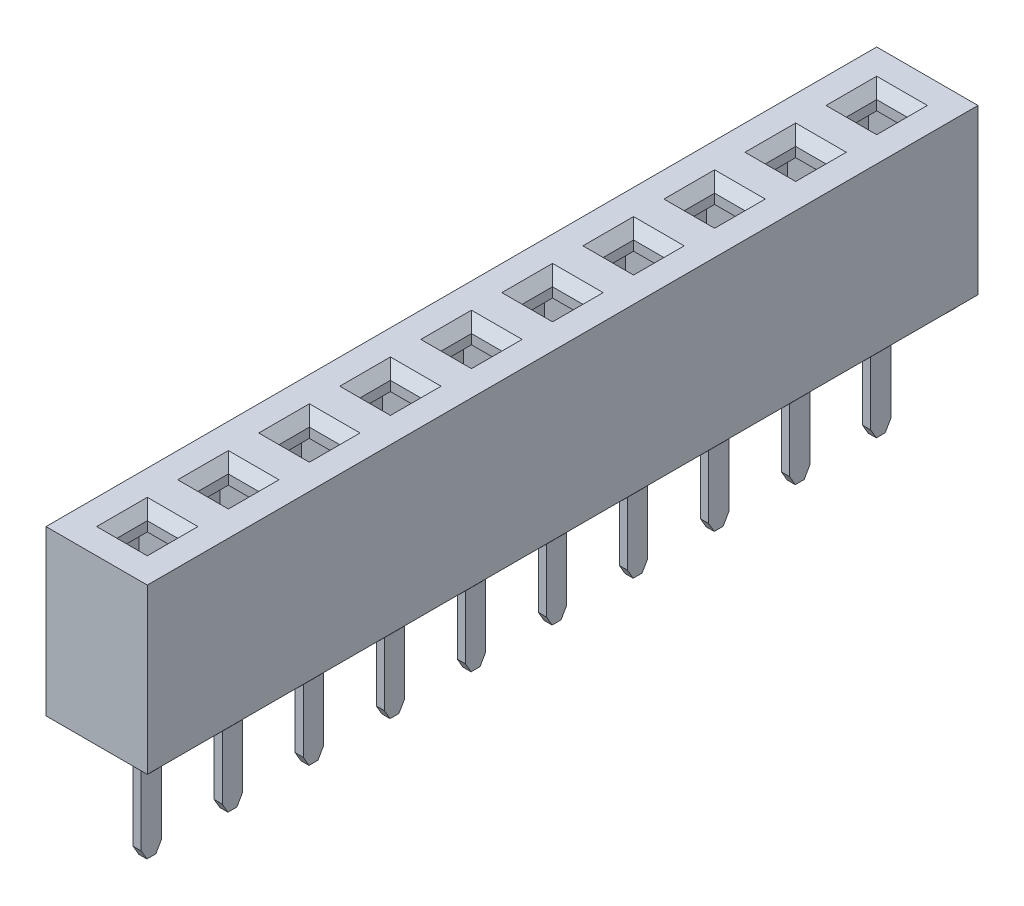
SolidWorks part; units mm, degrees
ref_plane "Front Plane" through (0, 0, 0) normal (0, 0, 1) x (1, 0, 0)
ref_plane "Top Plane" through (0, 0, 0) normal (0, 1, 0) x (1, 0, 0)
ref_plane "Right Plane" through (0, 0, 0) normal (1, 0, 0) x (0, 0, -1)
sketch "Sketch1" plane through (0, 0, 0) normal (1, 0, 0) x (0, 0, -1)
  line L0 (-1, -2.15) -> (1, -2.15)
  line L1 (-10.25, -2.15) -> (10.25, -2.15)
  line L2 (-10.25, -2.15) -> (-10.25, 2.15)
  line L3 (-10.25, 2.15) -> (10.25, 2.15)
  line L4 (10.25, -2.15) -> (10.25, 2.15)
  line L5 (-10.25, -2.15) -> (10.25, 2.15) construction
  line L6 (-10.25, 2.15) -> (10.25, -2.15) construction
  line L7 (-1, -2.15) -> (-1, -4.85) construction
  line L8 (-1.25, -4.85) -> (-0.75, -4.85)
  point P0 (0, 0)
  point P9 (0, -2.15)
  point P13 (-1, -4.85)
  dimension "D1" = 0.5
  dimension "Body Width" = 20.5
  dimension "Body Length" = 4.3
  dimension "For Hole Center to Center" = 2
  dimension "Termination Contact Length" = 2.7
  dimension "Overall Length" = 7
sketch "Sketch3" plane through (0, 0, 0) normal (0, 1, 0) x (1, 0, 0)
  line L1 (1.25, -10.25) -> (-1.25, -10.25)
  line L2 (1.25, -10.25) -> (1.25, 10.25)
  line L3 (1.25, 10.25) -> (-1.25, 10.25)
  line L4 (-1.25, -10.25) -> (-1.25, 10.25)
  line L5 (1.25, -10.25) -> (-1.25, 10.25) construction
  line L6 (1.25, 10.25) -> (-1.25, -10.25) construction
  point P0 (0, 0)
  dimension "D1" = 2.5
sketch "Sketch2" plane through (0, 0, 0) normal (1, 0, 0) x (0, 0, -1)
  line L0 (-10.25, 2.15) -> (10.25, 2.15)
  line L1 (10.25, 2.15) -> (10.25, -2.15)
  line L2 (10.25, -2.15) -> (-10.25, -2.15)
  line L3 (-10.25, -2.15) -> (-10.25, 2.15)
extrude "Boss-Extrude1" add sketch "Sketch2" against normal up to vertex (1.25 mm away) and the other way up to vertex (1.25 mm away) up to point (-1.25, 0, -10.25) other way up to point (1.25, 0, -10.25)
sketch "Sketch4" plane through (0, 2.15, 0) normal (0, 1, 0) x (1, 0, 0)
  line L0 (0, -10.25) -> (0, 10.25) construction
  line L1 (0.625, -9.625) -> (-0.625, -9.625)
  line L2 (0.625, -9.625) -> (0.625, -8.375)
  line L3 (0.625, -8.375) -> (-0.625, -8.375)
  line L4 (-0.625, -9.625) -> (-0.625, -8.375)
  line L5 (0.625, -9.625) -> (-0.625, -8.375) construction
  line L6 (0.625, -8.375) -> (-0.625, -9.625) construction
  point P0 (0, -9)
  dimension "D1" = 9
  dimension "D2" = 1.25
extrude "Cut-Extrude1" cut sketch "Sketch4" against normal through all draft 45
sketch "Sketch5" plane through (0, 2.15, 0) normal (0, 1, 0) x (1, 0, 0)
  line L1 (0.375, -9.375) -> (-0.375, -9.375)
  line L2 (0.375, -9.375) -> (0.375, -8.625)
  line L3 (0.375, -8.625) -> (-0.375, -8.625)
  line L4 (-0.375, -9.375) -> (-0.375, -8.625)
  line L5 (0.375, -9.375) -> (-0.375, -8.625) construction
  line L6 (0.375, -8.625) -> (-0.375, -9.375) construction
  point P0 (0, -9)
  dimension "D1" = 0.75
extrude "Cut-Extrude2" cut sketch "Sketch5" against normal through all
sketch "Sketch6" plane through (0, -2.15, 0) normal (0, -1, 0) x (1, 0, 0)
  line L0 (0, 10.25) -> (0, -10.25) construction
  line L1 (-0.7, 9.7) -> (0.7, 9.7)
  line L2 (-0.7, 9.7) -> (-0.7, 8.3)
  line L3 (-0.7, 8.3) -> (0.7, 8.3)
  line L4 (0.7, 9.7) -> (0.7, 8.3)
  line L5 (-0.7, 9.7) -> (0.7, 8.3) construction
  line L6 (-0.7, 8.3) -> (0.7, 9.7) construction
  line L7 (0.375, 9.375) -> (0.375, 8.625) construction
  line L8 (0.375, 8.625) -> (-0.375, 8.625) construction
  point P0 (0, 9)
  point P9 (0.375, 9)
  point P12 (0, 8.625)
  dimension "D1" = 1.4
extrude "Cut-Extrude3" cut sketch "Sketch6" against normal blind 3.81
sketch "Sketch7" plane through (0, -2.15, 0) normal (0, -1, 0) x (1, 0, 0)
  line L0 (-1.25, 9.7) -> (1.25, 9.7)
  line L1 (-1.25, 10.25) -> (-1.25, -10.25) construction
  line L2 (1.25, 10.25) -> (1.25, -10.25) construction
  line L3 (-1.25, 8.3) -> (1.25, 8.3)
  line L5 (-0.7, 8.3) -> (0.7, 8.3) construction
  line L6 (0.7, 9.7) -> (-0.7, 9.7) construction
  line L7 (1.25, 9.7) -> (1.25, 8.3)
  line L8 (-1.25, 8.3) -> (-1.25, 9.7)
extrude "Cut-Extrude4" cut sketch "Sketch7" against normal blind 0.254
pattern_linear "LPattern1" count 10 spacing 2 along (0, 0, -1) of "Cut-Extrude1", "Cut-Extrude2", "Cut-Extrude3", "Cut-Extrude4"
sketch "Sketch8" plane through (0, -2.15, 0) normal (0, -1, 0) x (1, 0, 0)
  line L0 (1.25, 9.975) -> (-1.25, 9.975)
  line L1 (1.25, 10.25) -> (1.25, 9.7) construction
  line L2 (-1.25, 10.25) -> (-1.25, 9.7) construction
  line L3 (-1.25, 9.975) -> (-1.25, 10.25)
  line L4 (-1.25, 10.25) -> (1.25, 10.25)
  line L5 (1.25, 10.25) -> (1.25, 9.975)
  line L6 (1.25, -9.975) -> (1.25, -10.25)
  line L7 (1.25, -9.7) -> (1.25, -10.25) construction
  line L8 (1.25, -10.25) -> (-1.25, -10.25)
  line L9 (-1.25, -10.25) -> (-1.25, -9.975)
  line L10 (-1.25, -9.7) -> (-1.25, -10.25) construction
  line L11 (-1.25, -9.975) -> (1.25, -9.975)
extrude "Cut-Extrude5" cut sketch "Sketch8" against normal up to surface (0.254 mm away) up to face at (-0.975, -1.896, -9)
sketch "Sketch9" plane through (0, 1.66, 0) normal (0, -1, 0) x (1, 0, 0)
  line L0 (-0.7, 9.7) -> (0.7, 9.7)
  line L1 (0.7, 9.7) -> (0.7, 8.3)
  line L2 (0.7, 8.3) -> (-0.7, 8.3)
extrude "Extrude-Thin1" add sketch "Sketch9" along normal offset from surface (3.356 mm away) 0.2 separate body thin up to face at (-0.975, -1.896, 9) thin type one direction wall 0.2
ref_plane "Plane1" through (0, 0, 9) normal (0, 0, 1) x (1, 0, 0)
sketch "Sketch10" plane through (0, 0, 9) normal (0, 0, 1) x (1, 0, 0)
  line L0 (0.7, -1.696) -> (0.1, -2.65)
  line L1 (0, 1.66) -> (0, -1.696) construction
  line L2 (-0.7, 1.66) -> (0.7, 1.66) construction
  line L3 (0.7, -1.696) -> (-0.7, -1.696) construction
  line L4 (0.1, -2.65) -> (0.1, -4.85)
  line L5 (0.1, -4.85) -> (-0.1, -4.85)
  line L6 (-0.1, -4.85) -> (-0.1, -2.65)
  line L7 (-0.1, -2.65) -> (0.5, -1.696)
  line L8 (0.5, -1.696) -> (0.7, -1.696)
  line L9 (0.5, -1.696) -> (0.5, 1.66) construction
  line L10 (-1.25, -2.15) -> (1.25, -2.15) construction
  point P18 (0, -4.85)
  dimension "D1" = 0.5
extrude "Boss-Extrude2" add sketch "Sketch10" along normal mid plane 0.5
sketch "Sketch11" plane through (0, -2.15, 0) normal (0, -1, 0) x (1, 0, 0)
  line L0 (-1.25, -10.25) -> (-1, -10.25)
  line L1 (-1.25, -10.25) -> (1.25, -10.25) construction
  line L2 (-1, -10.25) -> (-1, 10.25)
  line L3 (1.25, 10.25) -> (-1.25, 10.25) construction
  line L4 (-1, 10.25) -> (-1.25, 10.25)
  line L5 (-1.25, 10.25) -> (-1.25, -10.25)
  line L6 (1, -10.25) -> (1, 10.25)
  line L7 (1, 10.25) -> (1.25, 10.25)
  line L8 (1.25, 10.25) -> (1.25, -10.25)
  line L9 (1.25, -10.25) -> (1, -10.25)
  dimension "D1" = 0.25
extrude "Cut-Extrude6" cut sketch "Sketch11" against normal up to surface (0.254 mm away) up to face at (0, -1.896, -10.1125)
chamfer "Chamfer1" distance 0.1397 angle 60 1 edges at (0, -4.85, 9.25) first distance on face at (0, -4.85, 9)
chamfer "Chamfer2" distance 0.1397 angle 60 1 edges at (0, -4.85, 8.75) first distance on face at (0, -4.85, 8.9302)
fillet "Fillet1" radius 0.0762 6 edges at (0.1, -2.65, 9) (0.5, -0.018, 9.5) (0.5, -0.018, 8.5) (-0.1, -2.65, 9) (0.6, -1.696, 8.75) (0.6, -1.696, 9.25)
pattern_linear "LPattern2" count 10 spacing 2 along (0, 0, -1) of bodies 112
sketch "Sketch12" plane through (0, 2.15, 0) normal (0, 1, 0) x (1, 0, 0)
  line L0 (-0.625, -0.375) -> (0.625, -1.625) construction
  line L1 (-0.625, -1.625) -> (0.625, -0.375) construction
  circle A0 centre (0, -1) radius 0.8839
